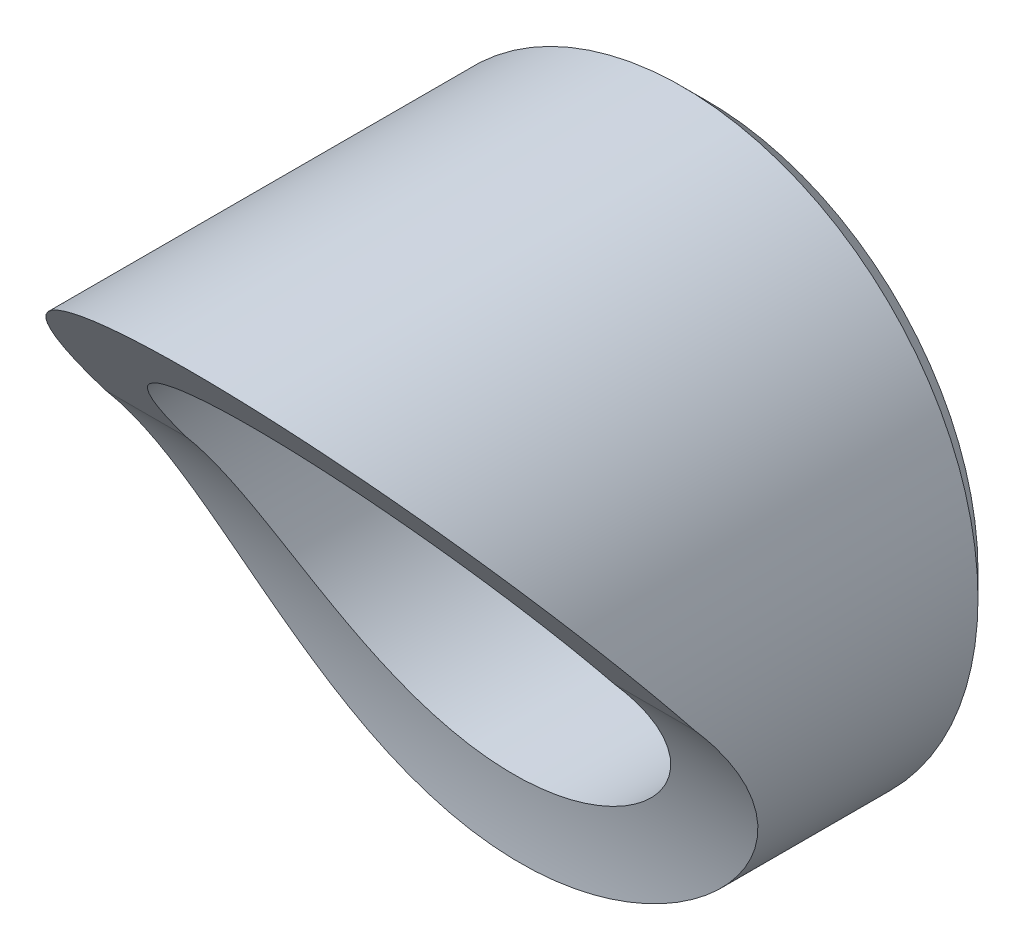
SolidWorks part; units mm, degrees
ref_plane "前视基准面" through (0, 0, 0) normal (0, 0, 1) x (1, 0, 0)
ref_plane "上视基准面" through (0, 0, 0) normal (0, 1, 0) x (1, 0, 0)
ref_plane "右视基准面" through (0, 0, 0) normal (1, 0, 0) x (0, 0, -1)
sketch "草图1" plane through (0, 0, 0) normal (0, 0, 1) x (1, 0, 0)
  circle A0 centre (0, 0) radius 12
  dimension "D1" = 24
extrude "凸台-拉伸1" add sketch "草图1" along normal blind 21
sketch "草图2" plane through (0, 0, 0) normal (1, 0, 0) x (0, 0, -1)
  line L0 (-21, 12) -> (-12.4517, 1.0587)
  line L1 (5.9306, -12) -> (-41.3368, -12) construction
  line L2 (-21, 12) -> (-21, -12)
  line L3 (-21, 12) -> (-21, -12) construction
  line L4 (-21, -12) -> (-7.6, -12)
  arc A0 (-7.6, -12) -> (-12.4517, 1.0587) centre (-27.6, -12) ccw
  dimension "D1" = 40
  dimension "D2" = 27.6
  dimension "D3" = 52
extrude "切除-拉伸1" cut sketch "草图2" against normal blind 21 and the other way blind 21
hole_wizard "M20 螺纹孔2" positions "草图19" profile "草图20" tap size "M20" standard "GB" end condition through all
sketch "草图19" plane through (0, 0, 0) normal (0, 0, -1) x (-1, 0, 0)
  point P0 (0, 0)
cosmetic thread "孔螺蚊线2"
sketch "草图20" plane through (0, 0, 0) normal (1, 0, 0) x (0, 1, 0)
  line L0 (0, 0) -> (0, 21)
  line L1 (0, 21) -> (8.75, 21)
  line L2 (8.75, 21) -> (8.75, 0)
  line L5 (8.75, 0) -> (0, 0)
  line L11 (0, -6.35) -> (0, 107.95) construction
  dimension "通孔螺纹孔钻头直径" = 17.5
  dimension "通孔螺纹孔钻头深度" = 21
chamfer "倒角2" distance 1 angle 45 1 edges at (12, 0, 0)
